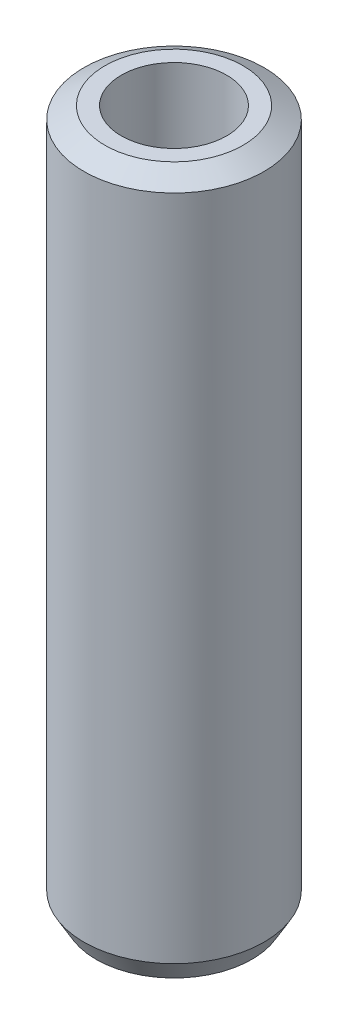
SolidWorks part; units mm, degrees
ref_plane "Front Plane" through (0, 0, 0) normal (0, 0, 1) x (1, 0, 0)
ref_plane "Top Plane" through (0, 0, 0) normal (0, 1, 0) x (1, 0, 0)
ref_plane "Right Plane" through (0, 0, 0) normal (1, 0, 0) x (0, 0, -1)
sketch "Sketch1" plane through (0, 0, 0) normal (0, 1, 0) x (1, 0, 0)
  circle A0 centre (0, 0) radius 30
  dimension "SHAFT_OD" = 60
extrude "Boss-Extrude1" add sketch "Sketch1" along normal blind 233.3541
sketch "Sketch2" plane through (0, 0, 0) normal (0, 1, 0) x (1, 0, 0)
  circle A0 centre (0, 0) radius 17.5481
  dimension "BORE_D" = 35.0961
extrude "Cut-Extrude1" cut sketch "Sketch2" along normal through all
chamfer "Chamfer1" distance 4.0432 angle 60 2 edges at (0, 233.3541, 30) (0, 0, 30) first distance on face at (0, 233.3541, 30) first distance on face at (0, 0, 17.5481)
